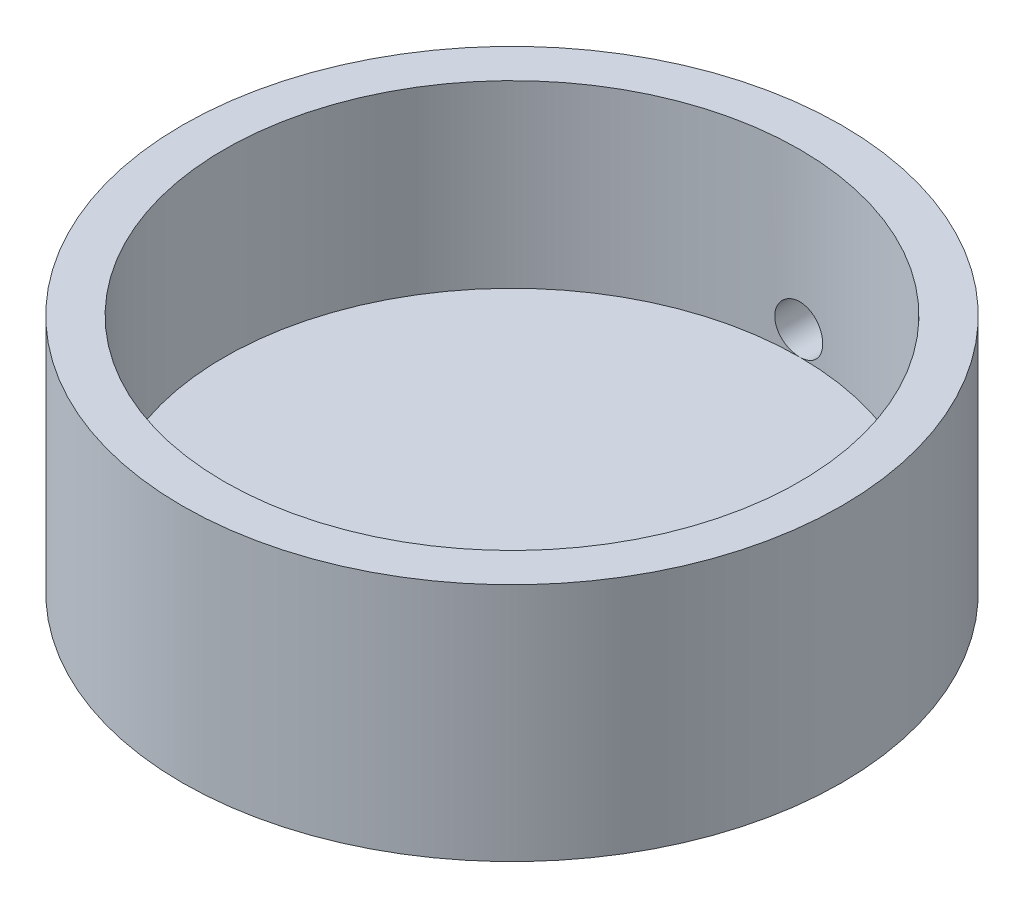
SolidWorks part; units mm, degrees
ref_plane "Front Plane" through (0, 0, 0) normal (0, 0, 1) x (1, 0, 0)
ref_plane "Top Plane" through (0, 0, 0) normal (0, 1, 0) x (1, 0, 0)
ref_plane "Right Plane" through (0, 0, 0) normal (1, 0, 0) x (0, 0, -1)
sketch "Sketch1" plane through (0, 0, 0) normal (0, 1, 0) x (1, 0, 0)
  circle A0 centre (0, 0) radius 27.5
  point P3 (0, 0)
  dimension "D1" = 55
extrude "Boss-Extrude1" add sketch "Sketch1" along normal blind 5 contours A0
sketch "Sketch2" plane through (0, 5, 0) normal (0, 1, 0) x (1, 0, 0)
  circle A0 centre (0, 0) radius 27.5
  circle A1 centre (0, 0) radius 24
  circle A3 centre (0, 0) radius 27.5 construction
  dimension "D1" = 3.5
extrude "Boss-Extrude2" add sketch "Sketch2" along normal blind 15
sketch "Sketch3" plane through (0, 0, 0) normal (0, 0, 1) x (1, 0, 0)
  line L0 (0, -11) -> (0, 11) construction
  line L1 (0, 5) -> (4.0593, 5) construction
  line L2 (30.25, 0) -> (-30.25, 0) construction
  circle A0 centre (0, 7) radius 2
  dimension "D2" = 4
  dimension "D1" = 5
extrude "Cut-Extrude1" cut sketch "Sketch3" against normal blind 74
